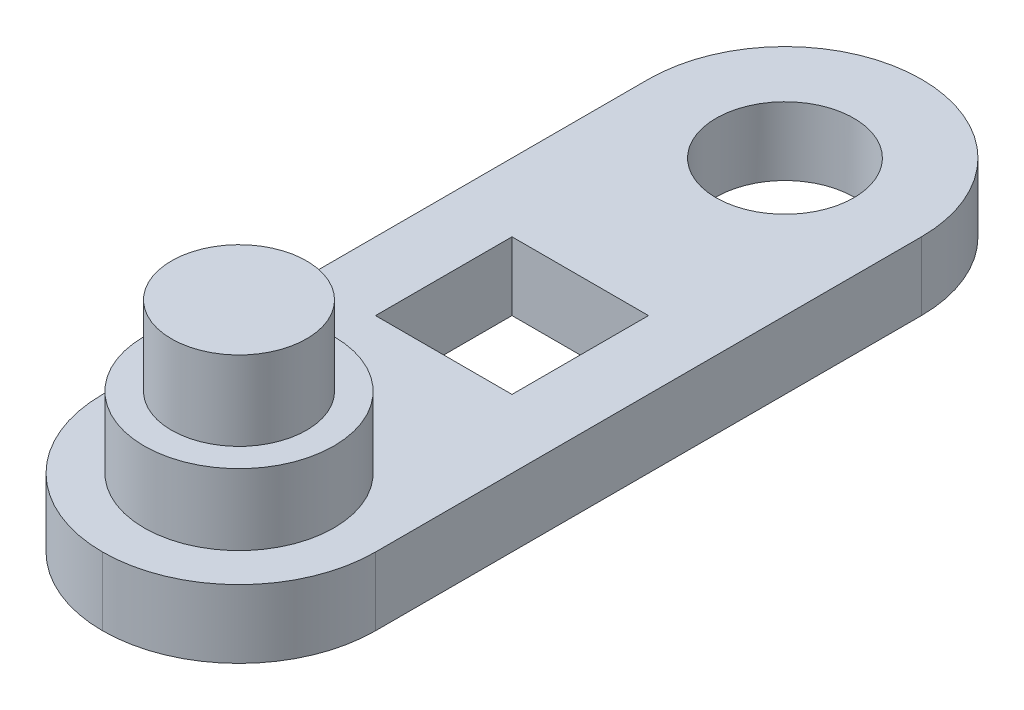
SolidWorks part; units mm, degrees
ref_plane "Front Plane" through (0, 0, 0) normal (0, 0, 1) x (1, 0, 0)
ref_plane "Top Plane" through (0, 0, 0) normal (0, 1, 0) x (1, 0, 0)
ref_plane "Right Plane" through (0, 0, 0) normal (1, 0, 0) x (0, 0, -1)
sketch "Sketch1" plane through (0, 0, 0) normal (0, 1, 0) x (1, 0, 0)
  line L0 (-23.3333, -31.0256) -> (-3.3333, -31.0256)
  line L2 (-23.3333, 28.9744) -> (-23.3333, -31.0256)
  line L4 (-3.3333, 28.9744) -> (-3.3333, -31.0256)
  line L5 (-23.3333, 28.9744) -> (-3.3333, 28.9744)
  dimension "D1" = 20
  dimension "D2" = 60
extrude "Boss-Extrude1" add sketch "Sketch1" along normal blind 5
fillet "Fillet1" radius 10 4 edges at (-23.3333, 2.5, -28.9744) (-3.3333, 2.5, -28.9744) (-23.3333, 2.5, 31.0256) (-3.3333, 2.5, 31.0256)
sketch "Sketch2" plane through (0, 5, 0) normal (0, 1, 0) x (1, 0, 0)
  circle A0 centre (-13.3333, 18.9744) radius 5.05
  circle A1 centre (-13.3333, -21.0256) radius 4.95
  dimension "D1" = 9.9
  dimension "D2" = 10.1
extrude "Boss-Extrude2" add sketch "Sketch2" along normal blind 11 contours A1
extrude "Cut-Extrude1" cut sketch "Sketch2<4>" against normal up to surface (5 mm away) contours A0 up to face at (-13.3333, 0, 1.0256)
sketch "Sketch2<4>" plane through (0, 5, 0) normal (0, 1, 0) x (1, 0, 0) same geometry as "Sketch2"
sketch "Sketch4" plane through (0, 5, 0) normal (0, 1, 0) x (1, 0, 0)
  line L0 (-3.3333, -21.0256) -> (-3.3333, 18.9744) construction
  line L1 (-18.3333, 3.9744) -> (-8.3333, 3.9744)
  line L2 (-18.3333, 3.9744) -> (-18.3333, -6.0256)
  line L3 (-18.3333, -6.0256) -> (-8.3333, -6.0256)
  line L4 (-8.3333, 3.9744) -> (-8.3333, -6.0256)
  circle A0 centre (-13.3333, 18.9744) radius 5.05 construction
  point P4 (-13.3333, 3.9744)
  dimension "D1" = 5
  dimension "D2" = 15
  dimension "D3" = 15
extrude "Cut-Extrude2" cut sketch "Sketch4" against normal up to surface (5 mm away) up to face at (-13.3333, 0, -24.0244)
sketch "Sketch5" plane through (0, 5, 0) normal (0, 1, 0) x (1, 0, 0)
  circle A0 centre (-13.3333, -21.0256) radius 6.95
  circle A1 centre (-13.3333, -21.0256) radius 4.95 construction
  dimension "D1" = 2
extrude "Boss-Extrude3" add sketch "Sketch5" along normal blind 5.2
